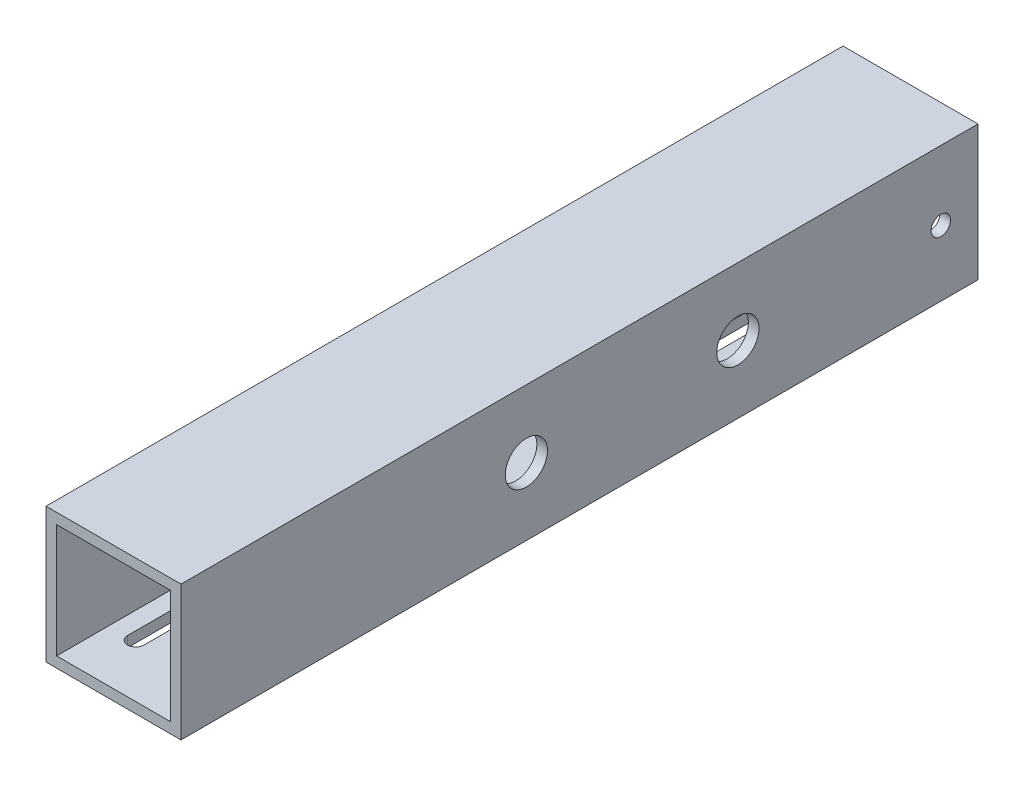
SolidWorks part; units mm, degrees
material "Acrylic (Medium-high impact)"
ref_plane "Front Plane" through (0, 0, 0) normal (0, 0, 1) x (1, 0, 0)
ref_plane "Top Plane" through (0, 0, 0) normal (0, 1, 0) x (1, 0, 0)
ref_plane "Right Plane" through (0, 0, 0) normal (1, 0, 0) x (0, 0, -1)
sketch "Sketch1" plane through (0, 0, 0) normal (0, 0, 1) x (1, 0, 0)
  line L1 (0, 0) -> (25.4, 0)
  line L2 (0, 0) -> (0, 25.4)
  line L3 (0, 25.4) -> (25.4, 25.4)
  line L4 (25.4, 0) -> (25.4, 25.4)
  line L5 (2, 23.4) -> (23.4, 23.4)
  line L6 (2, 23.4) -> (2, 2)
  line L7 (2, 2) -> (23.4, 2)
  line L8 (23.4, 23.4) -> (23.4, 2)
  dimension "D1" = 25.4
  dimension "D2" = 25.4
  dimension "D3" = 2
  dimension "D4" = 2
  dimension "D5" = 2
  dimension "D6" = 2
extrude "Boss-Extrude1" add sketch "Sketch1" along normal blind 150
sketch "Sketch2" plane through (25.4, 0, 0) normal (1, 0, 0) x (0, 0, -1)
  line L0 (0, 12.7) -> (-150, 12.7) construction
  line L1 (0, 0) -> (0, 25.4) construction
  line L2 (-150, 0) -> (-150, 25.4) construction
  circle A0 centre (-85, 12.7) radius 3.975
  circle A1 centre (-45.19, 12.7) radius 3.975
  dimension "D1" = 7.95
  dimension "D3" = 7.95
  dimension "D2" = 45.19
  dimension "D4" = 39.81
extrude "Cut-Extrude1" cut sketch "Sketch2" against normal blind 50
sketch "Sketch3" plane through (0, 0, 0) normal (0, -1, 0) x (1, 0, 0)
  line L0 (25.4, 150) -> (25.4, 0) construction
  line L2 (8.45, 140) -> (8.45, 80)
  line L3 (5.35, 90) -> (5.35, 150)
  line L4 (0, 150) -> (25.4, 150) construction
  circle A0 centre (6.9, 140) radius 1.55
  circle A1 centre (6.9, 90) radius 1.55
  dimension "D2" = 3.1
  dimension "D3" = 3.1
  dimension "D1" = 18.5
  dimension "D4" = 18.5
  dimension "D5" = 50
  dimension "D6" = 10
extrude "Cut-Extrude4" cut sketch "Sketch3" against normal blind 10 contours A1 L2 A0 L3 | A1 | A0 region at (6.9, 0, 140) region at (6.9, 0, 115) region at (6.9, 0, 90)
sketch "Sketch5" plane through (0, 0, 0) normal (-1, 0, 0) x (0, 0, 1)
  line L0 (0, 25.4) -> (0, 0) construction
  line L1 (0, 12.3331) -> (150, 12.7) construction
  line L2 (150, 25.4) -> (150, 0) construction
  circle A0 centre (7, 12.3502) radius 1.825
  dimension "D1" = 3.65
  dimension "D2" = 7
extrude "Cut-Extrude6" cut sketch "Sketch5" against normal up to surface (25.4 mm away) up to face at (25.4, 12.7, 41.215)
sketch "Sketch6" plane through (0, 0, 0) normal (0, -1, 0) x (1, 0, 0)
  line L0 (12.7, 0) -> (12.7, 150) construction
  line L1 (0, 0) -> (25.4, 0) construction
  line L2 (0, 150) -> (25.4, 150) construction
  line L3 (12.7, 5) -> (12.7, 45) construction
  line L4 (10.875, 5) -> (10.875, 45)
  line L5 (14.525, 5) -> (14.525, 45)
  arc A0 (10.875, 5) -> (14.525, 5) centre (12.7, 5) ccw
  arc A1 (14.525, 45) -> (10.875, 45) centre (12.7, 45) ccw
  point P8 (12.7, 25)
  dimension "D1" = 1.825
  dimension "D2" = 40
  dimension "D3" = 5
extrude "Cut-Extrude8" cut sketch "Sketch6" against normal blind 10
